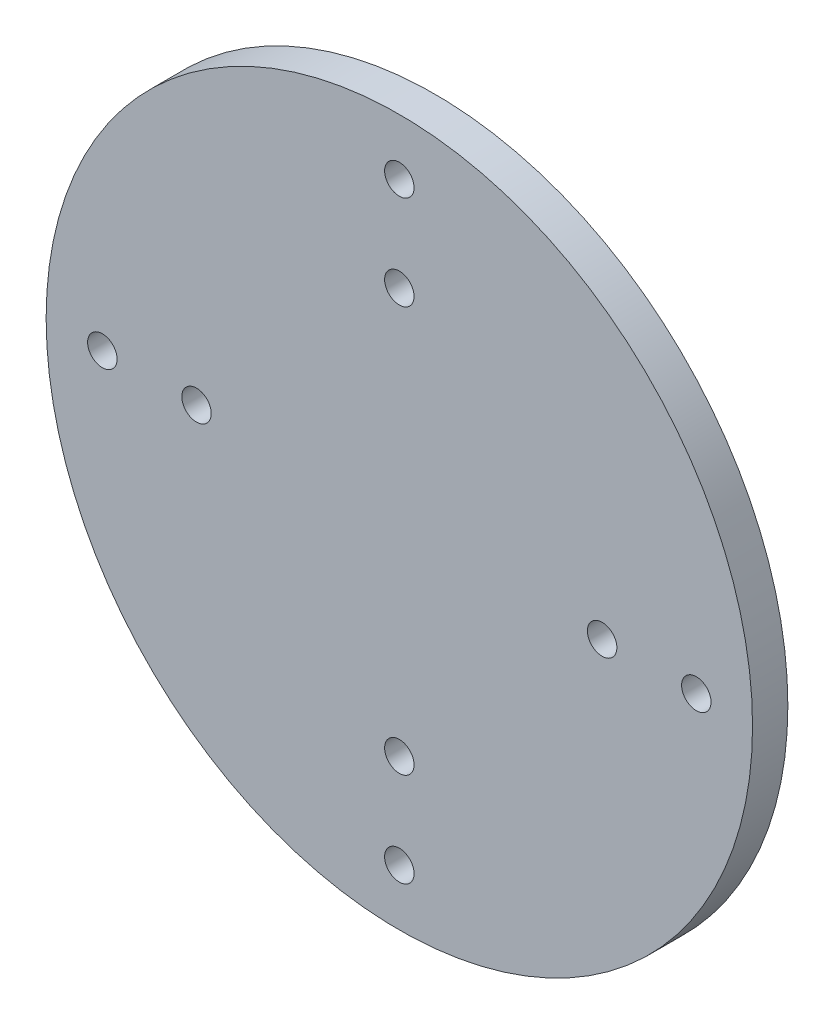
SolidWorks part; units mm, degrees
ref_plane "Front Plane" through (0, 0, 0) normal (0, 0, 1) x (1, 0, 0)
ref_plane "Top Plane" through (0, 0, 0) normal (0, 1, 0) x (1, 0, 0)
ref_plane "Right Plane" through (0, 0, 0) normal (1, 0, 0) x (0, 0, -1)
sketch "Sketch1" plane through (0, 0, 0) normal (0, 0, 1) x (1, 0, 0)
  circle A0 centre (124.7575, 5) radius 30
extrude "Boss-Extrude1" add sketch "Sketch1" along normal blind 3
hole_wizard "M3 Tapped Hole1" positions "Sketch3" profile "Sketch2" tap size "M3" standard "ISO"
sketch "Sketch3" plane through (0, 0, 0) normal (0, 0, -1) x (-1, 0, 0)
  point P0 (-107.5328, 5)
sketch "Sketch2" plane through (107.5328, 5, 0) normal (1, 0, 0) x (0, 1, 0)
  line L0 (0, 0) -> (0, 8.2511)
  line L1 (0, 8.2511) -> (1.25, 7.5)
  line L2 (1.25, 7.5) -> (1.25, 0)
  line L5 (1.25, 0) -> (0, 0)
  line L10 (0, 8.2511) -> (-1.25, 7.5) construction
  line L11 (0, -6.35) -> (0, 107.95) construction
  dimension "Tap Drill Dia." = 2.5
  dimension "Tap Drill Depth" = 7.5
  dimension "Drill Angle" = 118
cosmetic thread "Hole Thread1" parameters "D1"=3, "D2"=3
ref_axis "Axis1" through (124.7575, 5, 3) along (0, 0, -1)
pattern_linear "LPattern1" count 2 spacing 8 along (1, 0, 0) of "M3 Tapped Hole1"
pattern_circular "CirPattern1" count 4 over 360 about axis through (124.7575, 5, 3) along (0, 0, -1) of "LPattern1"
